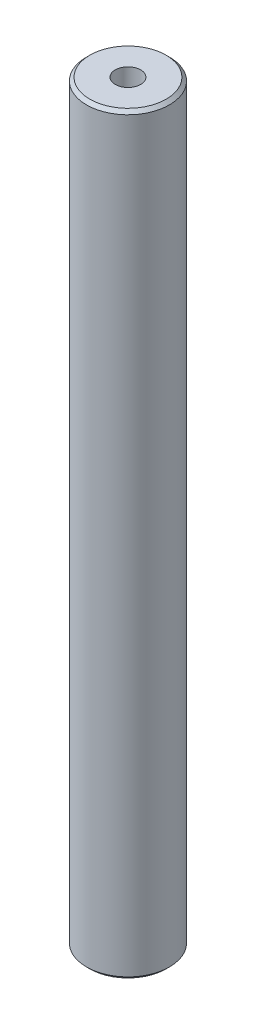
SolidWorks part; units mm, degrees
ref_plane "Front Plane" through (0, 0, 0) normal (0, 0, 1) x (1, 0, 0)
ref_plane "Top Plane" through (0, 0, 0) normal (0, 1, 0) x (1, 0, 0)
ref_plane "Right Plane" through (0, 0, 0) normal (1, 0, 0) x (0, 0, -1)
sketch "Sketch1" plane through (0, 0, 0) normal (0, 1, 0) x (1, 0, 0)
  circle A0 centre (0, 0) radius 32.5
  dimension "SHAFT_OD" = 65
extrude "Boss-Extrude1" add sketch "Sketch1" along normal blind 590.4392
sketch "Sketch2" plane through (0, 0, 0) normal (0, 1, 0) x (1, 0, 0)
  circle A0 centre (0, 0) radius 9.9541
  dimension "BORE_D" = 19.9082
extrude "Cut-Extrude1" cut sketch "Sketch2" along normal through all
chamfer "Chamfer1" distance 2.5844 angle 44.979 2 edges at (0, 590.4392, 32.5) (0, 0, 32.5) first distance on face at (0, 590.4392, 32.5) first distance on face at (0, 0, 9.9541)
